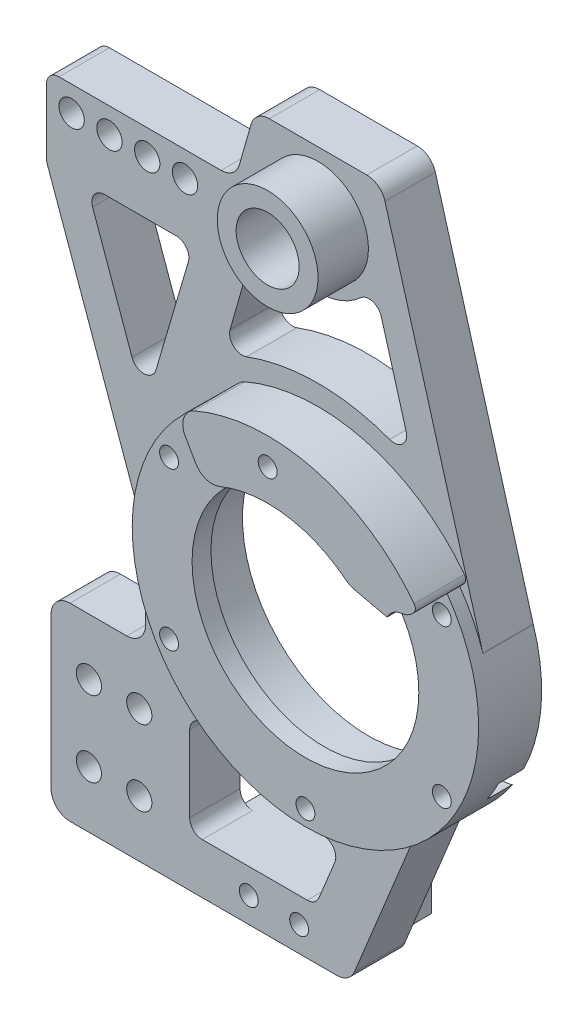
SolidWorks part; units mm, degrees
material "6061 合金"
ref_plane "前视基准面" through (0, 0, 0) normal (0, 0, 1) x (1, 0, 0)
ref_plane "上视基准面" through (0, 0, 0) normal (0, 1, 0) x (1, 0, 0)
ref_plane "右视基准面" through (0, 0, 0) normal (1, 0, 0) x (0, 0, -1)
other "Configuration Table"
sketch "草图1" plane through (0, 0, 0) normal (0, 0, 1) x (1, 0, 0)
  circle A0 centre (0, 0) radius 25
  circle A1 centre (0, 0) radius 20
  circle A2 centre (0, 0) radius 27.5
  circle A3 centre (0, 25) radius 1.5
  circle A4 centre (21.6506, 12.5) radius 1.5
  circle A5 centre (21.6506, -12.5) radius 1.5
  circle A6 centre (0, -25) radius 1.5
  circle A7 centre (-21.6506, -12.5) radius 1.5
  circle A8 centre (-21.6506, 12.5) radius 1.5
  point P20 (0, 0)
  dimension "D1" = 40
  dimension "D2" = 50
  dimension "D3" = 55
  dimension "D4" = 6
extrude "凸台-拉伸1" add sketch "草图1" along normal blind 8 contours A8 A0 A7 A6 A5 A4 A3 A1 | A2 A8 A0 A3 A4 A5 A6 A7
sketch "草图2" plane through (0, 0, 8) normal (0, 0, 1) x (1, 0, 0)
  line L0 (0, 0) -> (0, 65)
  line L1 (0, 65) -> (10, 65)
  line L2 (10, 65) -> (26.174, 8.4363)
  line L3 (0, 65) -> (-10, 65)
  line L4 (-10, 65) -> (-26.85, 5.9439)
  line L5 (-5.1919, 63.6281) -> (-5.22, 63.5294)
  line L6 (5.1927, 63.6254) -> (5.2201, 63.5294)
  line L7 (-5.1919, 63.6281) -> (-22.0418, 4.572) construction
  line L8 (5.1927, 63.6254) -> (21.3667, 7.0616) construction
  line L9 (-8.935, 50.5093) -> (-15.1412, 28.7575)
  line L10 (8.9402, 50.5197) -> (15.1668, 28.744)
  circle A0 centre (0, 55) radius 5
  circle A1 centre (0, 0) radius 27.5 construction
  circle A2 centre (0, 0) radius 20 construction
  circle A3 centre (0, 0) radius 27.5
  arc A4 (-8.935, 50.5093) -> (8.9402, 50.5197) centre (0, 55) ccw
  circle A5 centre (0, 55) radius 10 construction
  arc A6 (15.1668, 28.744) -> (-15.1412, 28.7575) centre (0, 0) ccw
  circle A7 centre (0, 0) radius 32.5 construction
  dimension "D1" = 10
  dimension "D4" = 10
  dimension "D5" = 55
  dimension "D2" = 10
  dimension "D3" = 10
  dimension "D6" = 5
  dimension "D7" = 5
  dimension "D8" = 5
  dimension "D9" = 5
extrude "凸台-拉伸2" add sketch "草图2" against normal blind 8
sketch "草图4" plane through (0, 0, 8) normal (0, 0, 1) x (1, 0, 0)
  line L0 (-27.3798, 2.5685) -> (-27.3798, -17.4315)
  line L1 (-27.3798, -17.4315) -> (-42.3798, -17.4315)
  line L2 (-42.3798, -17.4315) -> (-42.3798, -47.4315)
  line L3 (-42.3798, -47.4315) -> (5, -47.4315)
  line L4 (15, -50) -> (15, -23.0489)
  line L5 (15, -23.0489) -> (5, -47.4315)
  arc A0 (-25.9439, 9.1193) -> (26.174, 8.4363) centre (0, 0) ccw construction
  circle A1 centre (0, 0) radius 20 construction
  arc A2 (-27.3798, 2.5685) -> (15, -23.0489) centre (0, 0) ccw
  arc A5 (-27.3798, 2.5685) -> (15, -23.0489) centre (0, 0) ccw
  arc M14 (-25.9439, 9.1193) -> (26.174, 8.4363) centre (0, 0) ccw
  dimension "D1" = 15
  dimension "D2" = 30
  dimension "D3" = 50
  dimension "D4" = 15
extrude "凸台-拉伸3" add sketch "草图4" against normal blind 8 contours L5 L0 L1 L2 L3 M14
sketch "草图6" plane through (0, 0, 8) normal (0, 0, 1) x (1, 0, 0)
  line L0 (-42.3798, -17.4315) -> (-42.3798, -47.4315) construction
  line L1 (-42.3798, -47.4315) -> (5, -47.4315) construction
  line L5 (-20.3798, -39.4315) -> (-20.3798, -21.0392)
  line L6 (-27.3798, -17.4315) -> (-42.3798, -17.4315) construction
  line L7 (-0.3657, -39.4315) -> (-42.3798, -39.4315)
  line L8 (7.5983, -20.0132) -> (-0.3657, -39.4315)
  line L9 (-0.3657, -39.4315) -> (-20.3798, -39.4315)
  line L10 (3.9, -29.0306) -> (-0.3657, -39.4315)
  circle A0 centre (-36.3798, -26.4315) radius 2
  circle A1 centre (-28.3798, -26.4315) radius 2
  circle A2 centre (-28.3798, -38.4315) radius 2
  circle A3 centre (-36.3798, -38.4315) radius 2
  circle A4 centre (0, 0) radius 29.2914
  dimension "D3" = 4
  dimension "D4" = 6
  dimension "D5" = 9
  dimension "D8" = 9
  dimension "D9" = 8
  dimension "D7" = 8
  dimension "D6" = 8
  dimension "D1" = 2
  dimension "D2" = 2
extrude "切除-拉伸1" cut sketch "草图6" against normal blind 8 contours A4 L5 L9 L10 | A1 | A0 | A3 | A2
fillet "圆角1" radius 2 4 edges at (3.9, -29.0306, 4) (-0.3657, -39.4315, 4) (-20.3798, -39.4315, 4) (-20.3798, -21.0392, 4)
sketch "草图7" plane through (0, 0, 8) normal (0, 0, 1) x (1, 0, 0)
  line L0 (-13.119, 54.0685) -> (-43.119, 54.0685)
  line L1 (-10, 65) -> (-25.9439, 9.1193) construction
  line L2 (-42.3798, -47.4315) -> (5, -47.4315) construction
  line L3 (-43.119, 54.0685) -> (-43.119, 41.5)
  line L4 (-43.119, 41.5) -> (-27.3798, -2.5685)
  line L5 (-36.7478, 41.5) -> (-27.4726, 15.5301)
  line L7 (-36.7478, 41.5) -> (-19.8248, 41.5)
  line L10 (-37.4685, 43.5181) -> (-21.7294, -0.5504) construction
  line L11 (-19.8248, 41.5) -> (-27.4726, 15.5301)
  dimension "D1" = 30
  dimension "D2" = 101.5
  dimension "D3" = 6
extrude "凸台-拉伸5" add sketch "草图7" against normal blind 8
fillet "圆角2" radius 2 9 edges at (-43.119, 54.0685, 4) (-43.119, 41.5, 4) (-36.7478, 41.5, 4) (-19.8248, 41.5, 4) (-27.4726, 15.5301, 4) (15.1668, 28.744, 4) (-15.1412, 28.7575, 4) (-8.935, 50.5093, 4) (8.9402, 50.5197, 4)
fillet "圆角3" radius 3 10 edges at (-27.3798, -2.5685, 4) (-27.3798, -17.4315, 4) (-42.3798, -17.4315, 4) (-42.3798, -47.4315, 4) (5, -47.4315, 4) (15, -23.0489, 4) (26.174, 8.4363, 4) (10, 65, 4) (-10, 65, 4) (-13.119, 54.0685, 4)
sketch "草图8" plane through (0, 0, 8) normal (0, 0, 1) x (1, 0, 0)
  line L1 (-43.119, 52.0685) -> (-43.119, 41.8464) construction
  line L2 (-15.3827, 54.0685) -> (-41.119, 54.0685) construction
  circle A0 centre (-39.119, 50.0685) radius 2.01
  circle A1 centre (-33.119, 50.0685) radius 2.01
  circle A2 centre (-27.119, 50.0685) radius 2.01
  circle A3 centre (-21.119, 50.0685) radius 2.01
  dimension "D2" = 4.02
  dimension "D3" = 4
  dimension "D4" = 4
  dimension "D1" = 4
extrude "切除-拉伸2" cut sketch "草图8" against normal blind 8
sketch "草图9" plane through (0, 0, 8) normal (0, 0, 1) x (1, 0, 0)
  line L0 (-39.3798, -47.4315) -> (2.9879, -47.4315) construction
  circle A0 centre (-11, -43.4315) radius 1.5
  circle A1 centre (-3, -43.4315) radius 1.5
  circle A2 centre (0, 0) radius 20 construction
  dimension "D1" = 3
  dimension "D2" = 8
  dimension "D3" = 3
  dimension "D4" = 4
extrude "切除-拉伸3" cut sketch "草图9" against normal blind 8
sketch "草图10" plane through (0, 0, 8) normal (0, 0, 1) x (1, 0, 0)
  line L0 (-39.3798, -47.4315) -> (2.9879, -47.4315) construction
  line L1 (2, -47.4315) -> (-20, -47.4315)
  line L2 (2, -47.4315) -> (2, -39.4315)
  line L3 (2, -39.4315) -> (-20, -39.4315)
  line L4 (-20, -47.4315) -> (-20, -39.4315)
  circle A0 centre (-3, -43.4315) radius 1.5 construction
  dimension "D1" = 5
  dimension "D2" = 22
  dimension "D3" = 8
extrude "凸台-拉伸6" [suppressed] add sketch "草图10" along normal blind 8
sketch "草图12" [suppressed] plane through (0, 0, 8) normal (0, 0, -1) x (-1, 0, 0)
  circle A0 centre (11, -43.4315) radius 1.5
  circle A1 centre (3, -43.4315) radius 1.5
extrude "切除-拉伸4" [suppressed] cut sketch "草图12" against normal blind 8
sketch "草图13" [suppressed] plane through (0, -39.4315, 0) normal (0, 1, 0) x (1, 0, 0)
  line L1 (2, -16) -> (2, -8) construction
  line L2 (-20, -16) -> (-20, -8) construction
  line L3 (2, -16) -> (-20, -16) construction
  circle A0 centre (-15, -12) radius 1.5
  circle A1 centre (-7, -12) radius 1.5
  dimension "D1" = 5
  dimension "D2" = 9
  dimension "D3" = 8
  dimension "D4" = 4
  dimension "D5" = 3
  dimension "D6" = 3
  dimension "D8" = 4
  dimension "D7" = 8
extrude "切除-拉伸5" [suppressed] cut sketch "草图13" against normal blind 8
sketch "草图14" plane through (0, 0, 0) normal (0, 0, -1) x (-1, 0, 0)
  circle A0 centre (0, 55) radius 8
  circle A1 centre (0, 55) radius 5
extrude "凸台-拉伸7" add sketch "草图14" along normal blind 8
sketch "草图15" plane through (0, 0, 0) normal (0, 0, -1) x (-1, 0, 0)
  line L0 (0, 0) -> (16.25, 28.1458)
  line L1 (0, 0) -> (0, 11.0221)
  line L2 (-13.0073, 15.1925) -> (-26.7072, 12.0296)
  arc A0 (11.344, 30.4559) -> (-11.3641, 30.4484) centre (0, 0) ccw construction
  circle A2 centre (0, 0) radius 20 construction
  circle A4 centre (0, 0) radius 20
  circle A5 centre (0, 25) radius 1.5
  circle A6 centre (0, 0) radius 29.2914
  dimension "D1" = 30
  dimension "D2" = 77
extrude "凸台-拉伸8" add sketch "草图15" along normal blind 8 contours A4 L0 A6 L2 A5
fillet "圆角4" radius 3 1 edges at (-10, 17.3205, -4)
fillet "圆角6" radius 3 1 edges at (-14.6457, 25.3671, -4)
fillet "圆角9" radius 1 1 edges at (26.7072, 12.0296, -4)
fillet "圆角10" radius 3 1 edges at (13.0073, 15.1925, -4)
sketch "草图17" plane through (0, 0, -8) normal (0, 0, -1) x (-1, 0, 0)
  circle A0 centre (0, 25) radius 3
  circle A1 centre (21.6506, 12.5) radius 3
  circle A2 centre (21.6506, -12.5) radius 3
  circle A3 centre (0, -25) radius 3
  circle A4 centre (-21.6506, -12.5) radius 3
  circle A5 centre (-21.6506, 12.5) radius 3
  point P16 (0, 0)
  dimension "D1" = 6
extrude "切除-拉伸6" cut sketch "草图17" against normal blind 12
sketch "草图18" plane through (0, 0, -8) normal (0, 0, -1) x (-1, 0, 0)
  line L0 (-23.6413, 17.2938) -> (-28.4932, 13.9402)
  line L1 (-28.4932, 13.9402) -> (-24.9105, 10.3259)
  line L2 (-24.9105, 10.3259) -> (-23.875, 12.7891)
  arc A0 (-23.6413, 17.2938) -> (-23.875, 12.7891) centre (0, 13.8086) ccw
extrude "切除-拉伸7" cut sketch "草图18" against normal blind 8
fillet "圆角13" radius 3 1 edges at (23.8868, 14.4999, -4)
fillet "圆角14" radius 1 1 edges at (23.6413, 17.2938, -4)
sketch "草图19" plane through (0, 0, 8) normal (0, 0, 1) x (1, 0, 0)
  line L2 (13.698, 15.033) -> (18.9562, 13.8191)
  line L3 (-13.0598, 22.6203) -> (-11.4018, 19.7484)
  line L4 (13.698, 15.033) -> (18.9562, 13.8191)
  line L5 (-13.0598, 22.6203) -> (-11.4018, 19.7484)
  circle A0 centre (0, 55) radius 5
  circle A1 centre (0, 55) radius 8
  circle A2 centre (0, 55) radius 8
  arc A8 (23.2422, 17.8265) -> (-11.6555, 26.8726) centre (0, 0) ccw
  arc A9 (23.2367, 16.6022) -> (23.2422, 17.8265) centre (22.4487, 17.218) ccw
  arc A10 (21.2617, 15.4747) -> (23.2367, 16.6022) centre (20.8728, 18.4494) ccw
  arc A11 (21.2617, 15.4747) -> (18.9562, 13.8191) centre (21.6506, 12.5) ccw
  arc A12 (12.4981, 15.614) -> (13.698, 15.033) centre (14.3728, 17.9561) ccw
  arc A13 (12.4981, 15.614) -> (-7.6554, 18.4769) centre (0, 0) ccw
  arc A14 (-11.4018, 19.7484) -> (-7.6554, 18.4769) centre (-8.8037, 21.2484) ccw
  arc A15 (-11.6555, 26.8726) -> (-13.0598, 22.6203) centre (-10.4618, 24.1203) ccw
  arc A16 (23.2422, 17.8265) -> (-11.6555, 26.8726) centre (0, 0) ccw
  arc A17 (23.2367, 16.6022) -> (23.2422, 17.8265) centre (22.4487, 17.218) ccw
  arc A18 (21.2617, 15.4747) -> (23.2367, 16.6022) centre (20.8728, 18.4494) ccw
  arc A19 (21.2617, 15.4747) -> (18.9562, 13.8191) centre (21.6506, 12.5) ccw
  arc A20 (12.4981, 15.614) -> (13.698, 15.033) centre (14.3728, 17.9561) ccw
  arc A21 (12.4981, 15.614) -> (-7.6554, 18.4769) centre (0, 0) ccw
  arc A22 (-11.4018, 19.7484) -> (-7.6554, 18.4769) centre (-8.8037, 21.2484) ccw
  arc A23 (-11.6555, 26.8726) -> (-13.0598, 22.6203) centre (-10.4618, 24.1203) ccw
  dimension "D1" = 0
  dimension "D2" = 0
extrude "凸台-拉伸10" add sketch "草图19" along normal blind 8
sketch "草图20" plane through (0, 0, 0) normal (0, 1, 0) x (1, 0, 0)
  line L1 (-19.3566, 8.9295) -> (29.8135, 8.9295)
  line L2 (-19.3566, 8.9295) -> (-19.3566, 0)
  line L3 (-19.3566, 0) -> (29.8135, 0)
  line L4 (29.8135, 8.9295) -> (29.8135, 0)
extrude "切除-拉伸9" cut sketch "草图20" along normal through all
sketch "草图21" plane through (0, 0, 0) normal (0, 0, -1) x (-1, 0, 0)
  line L0 (39.3798, -47.4315) -> (-2.9879, -47.4315) construction
  line L1 (20, -39.4315) -> (-2, -39.4315)
  line L2 (20, -39.4315) -> (20, -47.4315)
  line L3 (20, -47.4315) -> (-2, -47.4315)
  line L4 (-2, -39.4315) -> (-2, -47.4315)
  circle A0 centre (3, -43.4315) radius 1.5 construction
  dimension "D1" = 22
  dimension "D2" = 8
  dimension "D3" = 5
extrude "凸台-拉伸11" add sketch "草图21" along normal blind 8
sketch "草图22" plane through (0, -39.4315, 0) normal (0, 1, 0) x (1, 0, 0)
  line L0 (-20, 8) -> (-20, 0) construction
  line L1 (-20, 8) -> (2, 8) construction
  circle A0 centre (-15, 4) radius 1.5
  circle A1 centre (-7, 4) radius 1.5
  dimension "D2" = 8
  dimension "D3" = 4
  dimension "D4" = 3
  dimension "D5" = 3
  dimension "D1" = 5
extrude "切除-拉伸10" cut sketch "草图22" against normal through all
sketch "草图23" plane through (0, 0, 0) normal (0, 0, 1) x (1, 0, 0)
  circle A0 centre (-11, -43.4315) radius 1.5
  circle A1 centre (-3, -43.4315) radius 1.5
extrude "切除-拉伸11" cut sketch "草图23" against normal through all
sketch "草图25" plane through (0, 0, 8) normal (0, 0, 1) x (1, 0, 0)
  circle A0 centre (0, 0) radius 20
  circle A1 centre (0, 0) radius 18
  dimension "D1" = 2
extrude "凸台-拉伸12" add sketch "草图25" against normal blind 1
sketch "草图26" plane through (0, 0, 8) normal (0, 0, 1) x (1, 0, 0)
  line L0 (-19.3504, 19.54) -> (-12.5727, 26.2519)
  circle A0 centre (0, 0) radius 27.5
  circle A1 centre (0, 0) radius 18
  arc A2 (-11.6555, 26.8726) -> (-13.0598, 22.6203) centre (-10.4618, 24.1203) ccw construction
  arc A3 (-12.5727, 26.2519) -> (-13.4585, 23.9816) centre (-10.4618, 24.1203) ccw
extrude "凸台-拉伸13" add sketch "草图26" along normal blind 2 contours A3 L0 A0 | A0 A1
sketch "草图28" plane through (0, 0, 8) normal (0, 0, -1) x (-1, 0, 0)
  circle A0 centre (0, 25) radius 1.5
  circle A1 centre (21.6506, 12.5) radius 1.5
  circle A2 centre (21.6506, -12.5) radius 1.5
  circle A3 centre (0, -25) radius 1.5
  circle A4 centre (-21.6506, -12.5) radius 1.5
  circle A5 centre (-21.6506, 12.5) radius 1.5
  point P15 (0, 0)
  dimension "D1" = 6
extrude "切除-拉伸12" cut sketch "草图28" against normal blind 10
